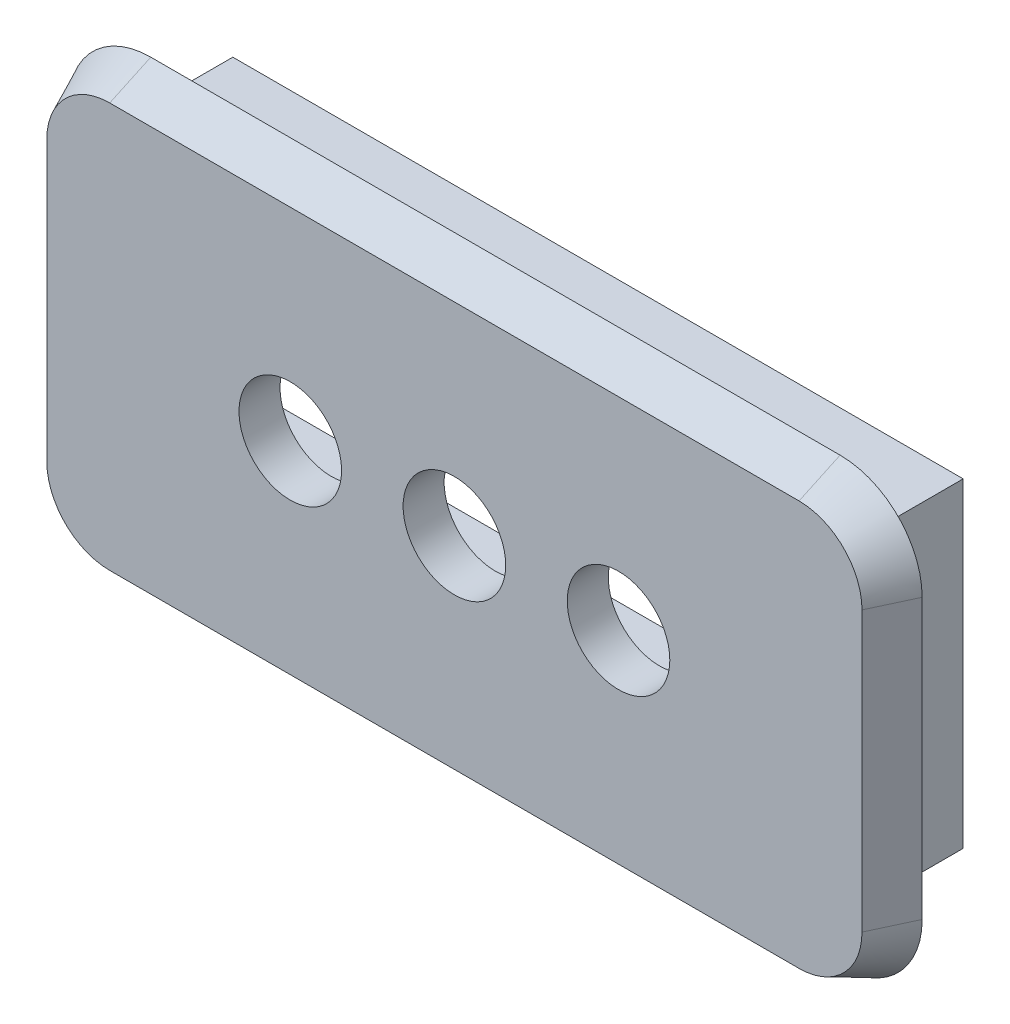
SolidWorks part; units mm, degrees
ref_plane "前视基准面" through (0, 0, 0) normal (0, 0, 1) x (1, 0, 0)
ref_plane "上视基准面" through (0, 0, 0) normal (0, 1, 0) x (1, 0, 0)
ref_plane "右视基准面" through (0, 0, 0) normal (1, 0, 0) x (0, 0, -1)
other "Configuration Table"
sketch "草图1" plane through (0, 0, 0) normal (0, 0, 1) x (1, 0, 0)
  line L4 (-7.465, 27.9) -> (-7.465, 22.1)
  line L5 (-7.465, 22.1) -> (8.335, 22.1)
  line L6 (8.335, 22.1) -> (8.335, 27.9)
  line L7 (8.335, 27.9) -> (-7.465, 27.9)
  line L12 (-8.465, 28.9) -> (-8.465, 21.1)
  line L13 (-8.465, 21.1) -> (9.335, 21.1)
  line L14 (9.335, 21.1) -> (9.335, 28.9)
  line L15 (9.335, 28.9) -> (-8.465, 28.9)
extrude "凸台-拉伸1" add sketch "草图1" against normal blind 2.5
sketch "草图2" plane through (0, 0, 0) normal (0, 0, 1) x (1, 0, 0)
  line L8 (10.835, 19.6) -> (10.835, 30.4)
  line L9 (-9.965, 19.6) -> (10.835, 19.6)
  line L10 (-9.965, 30.4) -> (-9.965, 19.6)
  line L11 (10.835, 30.4) -> (-9.965, 30.4)
  line L12 (10.835, 21.6) -> (10.835, 28.4)
  line L13 (-7.965, 19.6) -> (8.835, 19.6)
  line L14 (-9.965, 28.4) -> (-9.965, 21.6)
  line L15 (8.835, 30.4) -> (-7.965, 30.4)
  arc A0 (10.835, 28.4) -> (8.835, 30.4) centre (8.835, 28.4) ccw
  arc A1 (10.835, 21.6) -> (8.835, 19.6) centre (8.835, 21.6) cw
  arc A2 (-7.965, 19.6) -> (-9.965, 21.6) centre (-7.965, 21.6) cw
  arc A3 (-9.965, 28.4) -> (-7.965, 30.4) centre (-7.965, 28.4) cw
  dimension "D2" = 2
  dimension "D1" = 1.5
extrude "凸台-拉伸2" add sketch "草图2" along normal blind 1 draft 25
sketch "草图3" plane through (0, 0, 1) normal (0, 0, 1) x (1, 0, 0)
  line L0 (8.835, 29.9337) -> (-7.965, 29.9337) construction
  line L1 (-9.4987, 28.4) -> (-9.4987, 21.6) construction
  circle A0 centre (0.435, 25) radius 1.25
  circle A1 centre (-3.565, 25) radius 1.25
  circle A2 centre (4.435, 25) radius 1.25
  point P4 (0.435, 29.9337)
  point P7 (-9.4987, 25)
  point P12 (0, 0)
  point P13 (0, 0)
  point P14 (0, 0)
  dimension "D1" = 2.5
  dimension "D2" = 4
  dimension "D3" = 4
extrude "切除-拉伸1" cut sketch "草图3" against normal up to next
